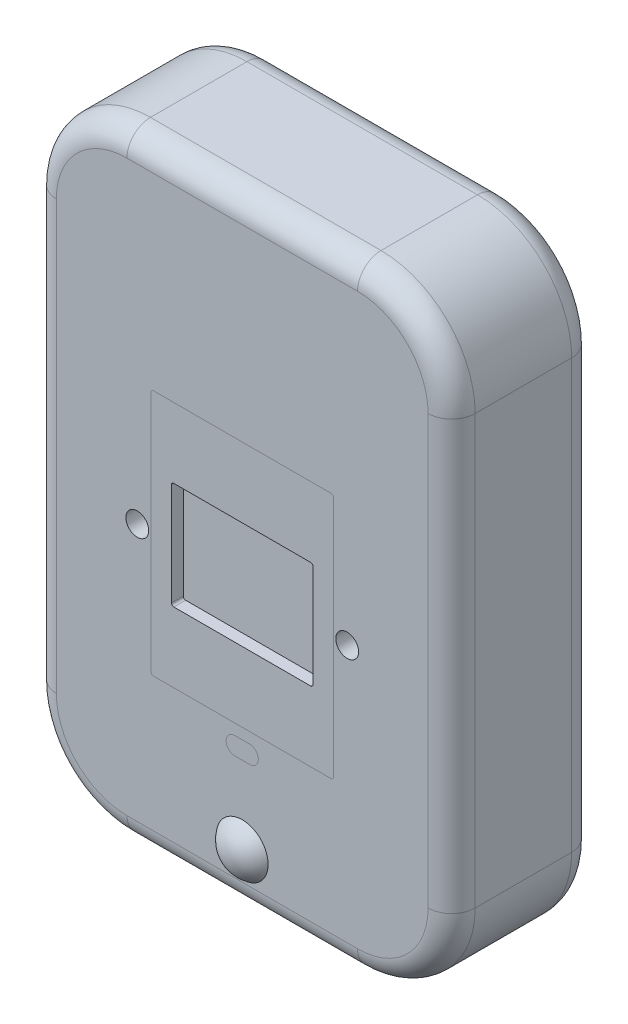
SolidWorks part; units mm, degrees
ref_plane "Front Plane" through (0, 0, 0) normal (0, 0, 1) x (1, 0, 0)
ref_plane "Top Plane" through (0, 0, 0) normal (0, 1, 0) x (1, 0, 0)
ref_plane "Right Plane" through (0, 0, 0) normal (1, 0, 0) x (0, 0, -1)
sketch "Sketch1" plane through (0, 0, 0) normal (0, 0, 1) x (1, 0, 0)
  line L0 (-88.9588, -10.9682) -> (89.0406, -11.4251) construction
  line L1 (-49, 131) -> (49, 131)
  line L2 (-89, 91) -> (-89, -91)
  line L3 (-49, -131) -> (49, -131)
  line L4 (89, 91) -> (89, -91)
  line L5 (-89, 131) -> (89, -131) construction
  line L6 (-89, -131) -> (89, 131) construction
  line L7 (0, 131) -> (0, -131) construction
  line L8 (-29.05, 11.25) -> (29.05, 11.25)
  line L9 (-30.05, 10.25) -> (-30.05, -33.25)
  line L10 (-29.05, -34.25) -> (29.05, -34.25)
  line L11 (30.05, 10.25) -> (30.05, -33.25)
  line L12 (-30.05, 11.25) -> (30.05, -34.25) construction
  line L13 (-30.05, -34.25) -> (30.05, 11.25) construction
  line L14 (-37.75, 41) -> (37.75, 41)
  line L15 (-38.75, 40) -> (-38.75, -63)
  line L16 (-37.75, -64) -> (37.75, -64)
  line L17 (38.75, 40) -> (38.75, -63)
  line L18 (-38.75, 41) -> (38.75, -64) construction
  line L19 (-38.75, -64) -> (38.75, 41) construction
  line L20 (-3.1, -72.35) -> (3.1, -72.35) construction
  line L21 (-3.1, -68.6) -> (3.1, -68.6)
  line L22 (-3.1, -76.1) -> (3.1, -76.1)
  arc A0 (-89, -91) -> (-49, -131) centre (-49, -91) ccw
  arc A1 (49, -131) -> (89, -91) centre (49, -91) ccw
  arc A2 (49, 131) -> (89, 91) centre (49, 91) cw
  arc A3 (-49, 131) -> (-89, 91) centre (-49, 91) ccw
  circle A6 centre (0, -109) radius 11 construction
  circle A7 centre (-44.6, -11.5) radius 4.8 construction
  circle A8 centre (44.6, -11.5) radius 4.8 construction
  arc A9 (29.05, 11.25) -> (30.05, 10.25) centre (29.05, 10.25) cw
  arc A10 (29.05, -34.25) -> (30.05, -33.25) centre (29.05, -33.25) ccw
  arc A11 (-30.05, -33.25) -> (-29.05, -34.25) centre (-29.05, -33.25) ccw
  arc A12 (-29.05, 11.25) -> (-30.05, 10.25) centre (-29.05, 10.25) ccw
  arc A13 (37.75, -64) -> (38.75, -63) centre (37.75, -63) ccw
  arc A14 (-38.75, -63) -> (-37.75, -64) centre (-37.75, -63) ccw
  arc A15 (37.75, 41) -> (38.75, 40) centre (37.75, 40) cw
  arc A16 (-37.75, 41) -> (-38.75, 40) centre (-37.75, 40) ccw
  arc A17 (-3.1, -68.6) -> (-3.1, -76.1) centre (-3.1, -72.35) ccw
  arc A18 (3.1, -76.1) -> (3.1, -68.6) centre (3.1, -72.35) ccw
  point P0 (0, 0)
  point P20 (0, -11.5)
  point P21 (0, -11.5)
  point P30 (0, -72.35)
  dimension "D1" = 40
  dimension "D11" = 22
  dimension "D12" = 89.2
  dimension "D13" = 9.6
  dimension "D14" = 1
  dimension "D15" = 1
  dimension "D18" = 6.2
  dimension "D2" = 178
  dimension "D3" = 178
  dimension "D4" = 262
  dimension "D5" = 11.5
  dimension "D6" = 60.1
  dimension "D7" = 45.5
  dimension "D8" = 105
  dimension "D9" = 77.5
  dimension "D10" = 109
  dimension "D16" = 60.85
  dimension "D17" = 7.5
extrude "Boss-Extrude1" add sketch "Sketch1" along normal mid plane 61 contours L1 A3 L2 A0 L3 A1 L4 A2 A16 L14 A15 L17 A13 L16 A14 L15 | L14 A16 L15 A14 L16 A13 L17 A15 A12 L8 A9 L11 A10 L10 A11 L9 | A16 L14 A15 L17 A13 L16 A14 L15 | L9 A11 L10 A10 L11 A9 L8 A12 | L2 A0 L3 A1 L4 A2 L1 A3 region at (0, 127.8325, 0) region at (0, 39.695, 0)
extrude "Cut-Extrude1" cut sketch "Sketch1<4>" against normal blind 5 from surface contours L8 A12 L9 A11 L10 A10 L11 A9 region at (0, -11.5, 0) starting at face at (0, 0, 30.5)
sketch "Sketch1<4>" plane through (0, 0, 0) normal (0, 0, 1) x (1, 0, 0) same geometry as "Sketch1"
split line "Split Line1"
sketch "Sketch1<6>" plane through (0, 0, 0) normal (0, 0, 1) x (1, 0, 0) same geometry as "Sketch1"
hole_wizard "CBORE for M4 SHCS1" positions "Sketch3" profile "Sketch2" counterbore size "M4" standard "ANSI Metric" end condition through all
sketch "Sketch3" plane through (0, 0, 30.5) normal (0, 0, 1) x (1, 0, 0)
  point P0 (-44.6, -11.5)
  point P3 (44.6, -11.5)
sketch "Sketch2" plane through (-44.6, -11.5, 30.5) normal (1, 0, 0) x (0, -1, 0)
  line L0 (0, 0) -> (0, 61)
  line L1 (0, 61) -> (2.25, 61)
  line L3 (2.25, 61) -> (2.25, 55.5)
  line L4 (2.25, 55.5) -> (4.85, 55.5)
  line L5 (4.85, 55.5) -> (4.85, 0)
  line L7 (4.85, 0) -> (0, 0)
  line L11 (0, -6.35) -> (0, 107.95) construction
  dimension "Thru Hole Dia." = 4.5
  dimension "Thru Hole Depth" = 61
  dimension "C'Bore Dia." = 9.7
  dimension "C'Bore Depth" = 55.5
hole_wizard "1/4-20 Tapped Hole1" positions "Sketch5" profile "Sketch7" tap size "1/4-20" standard "ANSI Inch"
sketch "Sketch5" plane through (0, 0, -30.5) normal (0, 0, -1) x (-1, 0, 0)
  line L0 (49, -131) -> (-49, -131) construction
  point P0 (0, 12)
  dimension "D1" = 143
sketch "Sketch7" plane through (0, 12, -30.5) normal (1, 0, 0) x (0, 1, 0)
  line L0 (0, 0) -> (0, 12)
  line L1 (0, 12) -> (2.5527, 12)
  line L2 (2.5527, 12) -> (2.5527, 0)
  line L5 (2.5527, 0) -> (0, 0)
  line L10 (0, 12) -> (-2.5527, 12) construction
  line L11 (0, -6.35) -> (0, 107.95) construction
  dimension "Tap Drill Dia." = 5.1054
  dimension "Tap Drill Depth" = 12
  dimension "Drill Angle" = 180
cosmetic thread "Hole Thread1" parameters "D1"=12, "D2"=6.35
sketch "Sketch4" plane through (0, 0, 0) normal (1, 0, 0) x (0, 0, -1)
  line L0 (-157.2816, -109) -> (143.2911, -109) construction
  line L8 (-30.5, 91) -> (-30.5, -91) construction
  line L9 (-30.5, -98) -> (0, -98) construction
  line L12 (-36.4, -109) -> (-9.9915, -109)
  arc A0 (-9.9915, -109) -> (-36.4, -109) centre (-23.1958, -109) ccw
  arc A1 (-36.4, -109) -> (-9.9915, -109) centre (-23.1958, -109) ccw construction
  dimension "D1" = 5.9
revolve "Revolve1" add sketch "Sketch4" angle 360 about L0
fillet "Fillet1" radius 10 16 edges at (-77.2843, -119.2843, -30.5) (-89, 0, -30.5) (-77.2843, 119.2843, -30.5) (0, 131, -30.5) (77.2843, 119.2843, -30.5) (89, 0, -30.5) (77.2843, -119.2843, -30.5) (-77.2843, -119.2843, 30.5) (-89, 0, 30.5) (-77.2843, 119.2843, 30.5) (0, 131, 30.5) (77.2843, 119.2843, 30.5) (89, 0, 30.5) (77.2843, -119.2843, 30.5) (0, -131, -30.5) (0, -131, 30.5)
sketch "Sketch8" plane through (-89, 0, 0) normal (-1, 0, 0) x (0, 0, 1)
  line L0 (20.5, 131) -> (-20.5, 131) construction
  line L1 (-7.55, 60.1) -> (7.55, 60.1)
  line L2 (-7.55, 60.1) -> (-7.55, 81)
  line L3 (-7.55, 81) -> (7.55, 81)
  line L4 (7.55, 60.1) -> (7.55, 81)
  line L5 (-7.55, 60.1) -> (7.55, 81) construction
  line L6 (-7.55, 81) -> (7.55, 60.1) construction
  point P0 (0, 70.55)
  dimension "D1" = 50
  dimension "D2" = 20.9
  dimension "D3" = 15.1
extrude "Boss-Extrude2" add sketch "Sketch8" along normal blind 5
ref_axis "Axis1" through (0, -11.5, 0) along (0, 0, 1)
